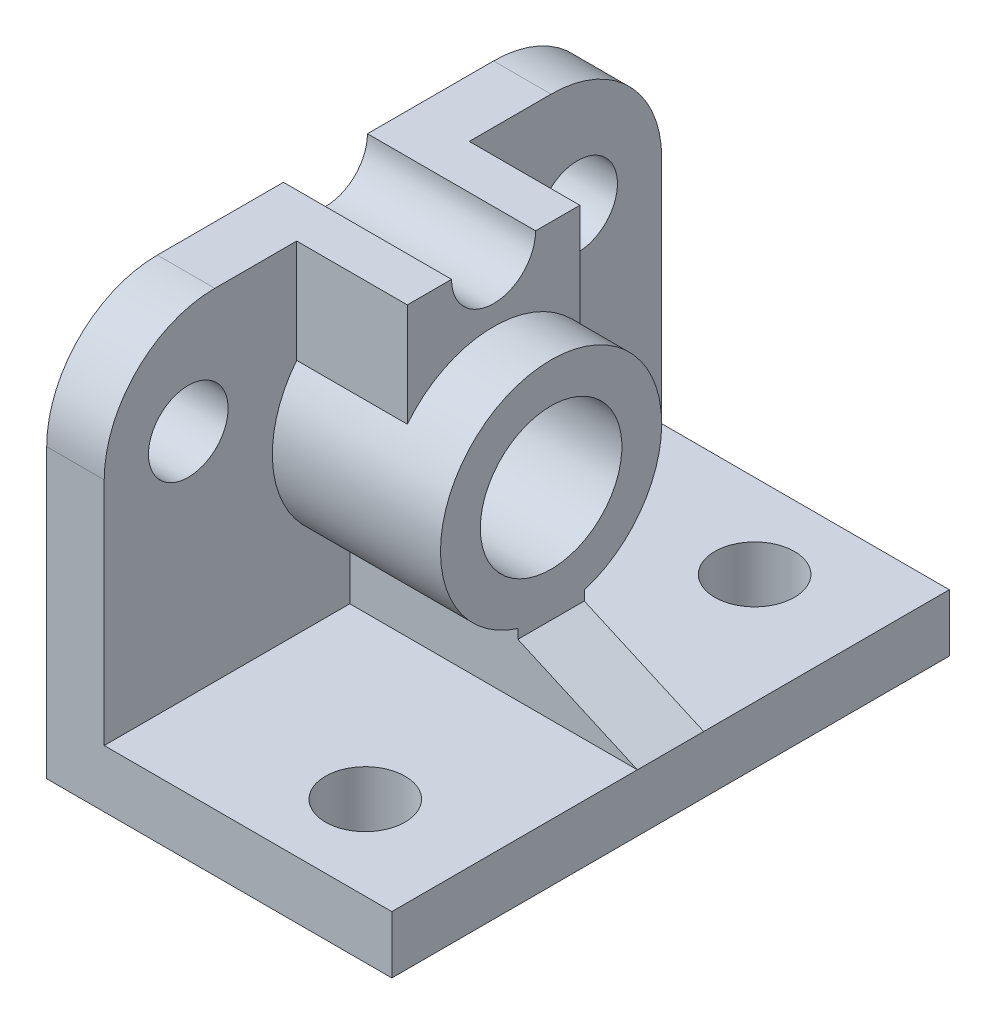
SolidWorks part; units mm, degrees
ref_plane "Front Plane" through (0, 0, 0) normal (0, 0, 1) x (1, 0, 0)
ref_plane "Top Plane" through (0, 0, 0) normal (0, 1, 0) x (1, 0, 0)
ref_plane "Right Plane" through (0, 0, 0) normal (1, 0, 0) x (0, 0, -1)
sketch "Sketch1" plane through (0, 0, 0) normal (0, 1, 0) x (1, 0, 0)
  line L0 (14, -44) -> (14, 44) construction
  line L1 (-39, -63) -> (39, -63)
  line L2 (-39, -63) -> (-39, 63)
  line L3 (-39, 63) -> (39, 63)
  line L4 (39, -63) -> (39, 63)
  line L5 (-39, -63) -> (39, 63) construction
  line L6 (-39, 63) -> (39, -63) construction
  circle A0 centre (14, -44) radius 9
  circle A1 centre (14, 44) radius 9
  point P0 (0, 0)
  dimension "D3" = 18
  dimension "D1" = 126
  dimension "D2" = 78
  dimension "D4" = 25
  dimension "D5" = 19
  dimension "D6" = 19
extrude "Boss-Extrude1" add sketch "Sketch1" along normal blind 13
sketch "Sketch2" plane through (-39, 0, 0) normal (-1, 0, 0) x (0, 0, 1)
  line L0 (63, 0) -> (63, 65)
  line L1 (-63, 0) -> (-63, 65)
  line L3 (-63, 0) -> (63, 0) construction
  line L4 (-63, 0) -> (63, 0)
  line L5 (0, 0) -> (0, 90) construction
  line L6 (-63, 13) -> (63, 13) construction
  line L8 (-9.5, 90) -> (-19.5, 90)
  line L9 (-19.5, 90) -> (-19.5, 66.6445)
  line L10 (19.5, 90) -> (19.5, 66.6445)
  line L11 (9.5, 90) -> (19.5, 90)
  line L12 (-38, 90) -> (-19.5, 90)
  line L13 (19.5, 90) -> (38, 90)
  circle A0 centre (44, 65) radius 9
  circle A1 centre (-44, 65) radius 9
  arc A2 (63, 65) -> (38, 90) centre (38, 65) ccw
  arc A3 (-63, 65) -> (-38, 90) centre (-38, 65) cw
  arc A4 (-9.5, 90) -> (9.5, 90) centre (0, 90) ccw
  circle A5 centre (0, 51) radius 16
  circle A6 centre (0, 51) radius 25
  point P12 (63, 90)
  point P19 (0, 13)
  line M9 (63, 13) -> (-63, 13)
  dimension "D2" = 18
  dimension "D6" = 25
  dimension "D7" = 19
  dimension "D8" = 38
  dimension "D9" = 32
  dimension "D10" = 50
  dimension "D11" = 39
  dimension "D13" = 6
  dimension "D1" = 90
  dimension "D3" = 19
  dimension "D4" = 19
  dimension "D5" = 10
  dimension "D12" = 52
  dimension "D14" = 63
extrude "Boss-Extrude2" add sketch "Sketch2" against normal blind 13 contours L5 L0 A2 L13 L10 A6 A0 M9 | L5 A6 L9 L12 A3 L1 A1 M9 region at (-39, 46.0541, 38.0707) region at (-39, 46.0541, -38.0707)
extrude "Boss-Extrude3" add sketch "Sketch2<3>" against normal blind 38 contours A6 L5 A4 L8 L9 | L5 A6 L10 L11 A4 region at (-39, 80.0997, 12.4158) region at (-39, 80.0997, -12.4158)
sketch "Sketch2<3>" plane through (-39, 0, 0) normal (-1, 0, 0) x (0, 0, 1) same geometry as "Sketch2"
extrude "Boss-Extrude4" add sketch "Sketch2<4>" against normal blind 51 contours L5 A6 A5 | A6 L5 A5 region at (-39, 40.4277, -22.0361) region at (-39, 30.5, 0.559)
sketch "Sketch2<4>" plane through (-39, 0, 0) normal (-1, 0, 0) x (0, 0, 1) same geometry as "Sketch2"
sketch "Sketch3" plane through (0, 0, 0) normal (0, 0, 1) x (1, 0, 0)
  line L0 (-26, 13) -> (39, 13) construction
  line L1 (-26, 13) -> (39, 13)
  line L2 (-26, 13) -> (-26, 25.0389)
  line L3 (-26, 13) -> (-26, 65) construction
  line L4 (39, 13) -> (12, 25.0389)
  line L5 (12, 25.0389) -> (-26, 25.0389)
  line L6 (12, 26) -> (12, 25.0389) construction
  dimension "D1" = 38
  dimension "D2" = 29.5624
extrude "Boss-Extrude5" add sketch "Sketch3" along normal mid plane 15
sketch "Sketch4" plane through (0, 25.0389, 0) normal (0, 1, 0) x (1, 0, 0)
  line L4 (12, 7.5) -> (-26, 7.5)
  line L5 (-26, 7.5) -> (-26, -7.5)
  line L6 (-26, -7.5) -> (12, -7.5)
  line L7 (12, -7.5) -> (12, 7.5)
  line L8 (12, 7.5) -> (-26, 7.5)
  line L9 (-26, 7.5) -> (-26, -7.5)
  line L10 (-26, -7.5) -> (12, -7.5)
  line L11 (12, -7.5) -> (12, 7.5)
  dimension "D1" = 0
extrude "Boss-Extrude6" add sketch "Sketch4" along normal up to surface (2.1126 mm away) up to face at (12, 51, 25)
